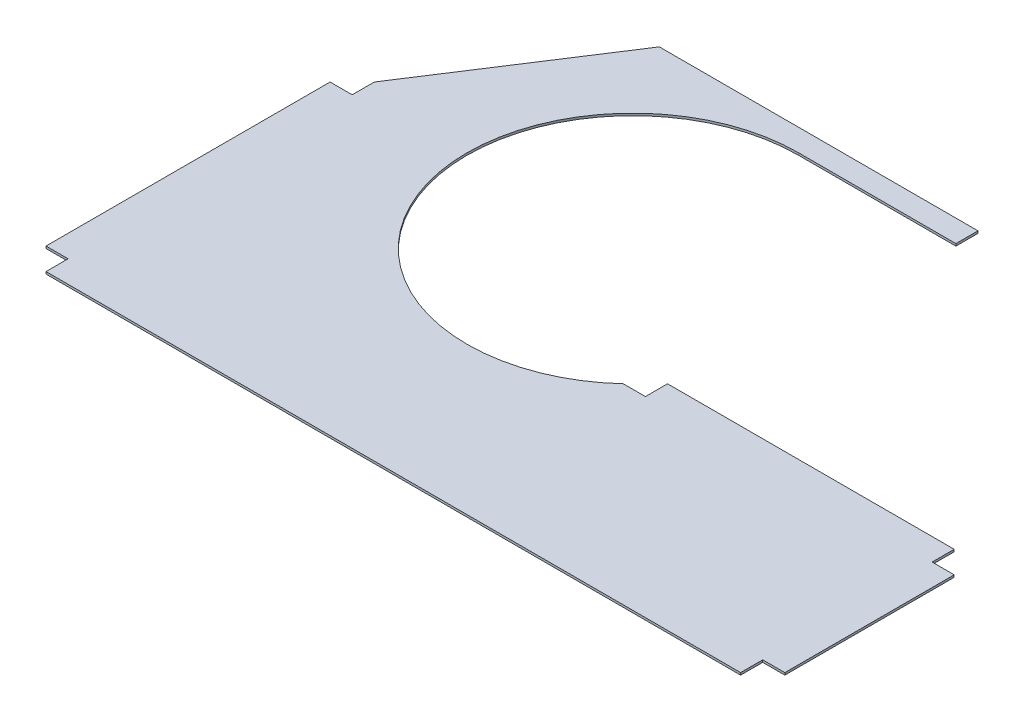
SolidWorks part; units mm, degrees
ref_plane "Front Plane" through (0, 0, 0) normal (0, 0, 1) x (1, 0, 0)
ref_plane "Top Plane" through (0, 0, 0) normal (0, 1, 0) x (1, 0, 0)
ref_plane "Right Plane" through (0, 0, 0) normal (1, 0, 0) x (0, 0, -1)
sketch "Sketch1" plane through (0, 0, 0) normal (0, 1, 0) x (1, 0, 0)
  line L0 (0, 0) -> (20, 0)
  line L1 (20, 0) -> (20, -20)
  line L2 (20, -20) -> (648.38, -20)
  line L3 (648.38, -20) -> (648.38, 0)
  line L4 (648.38, 0) -> (668.38, 0)
  line L5 (668.38, 0) -> (668.38, 153.21)
  line L7 (0, 0) -> (0, 257)
  line L9 (121.3895, 433.4594) -> (409.6583, 433.4594)
  line L10 (267.3398, 413.4594) -> (409.6583, 413.4594)
  line L11 (409.6583, 433.4594) -> (409.6583, 413.4594)
  line L12 (0, 257) -> (20, 257)
  line L13 (20, 257) -> (20, 277)
  line L14 (20, 277) -> (121.3895, 433.4594)
  line L15 (668.38, 153.21) -> (648.38, 153.21)
  line L16 (648.38, 153.21) -> (648.38, 173.21)
  line L18 (648.38, 173.21) -> (389.0505, 173.21)
  line L19 (389.0505, 173.21) -> (389.0505, 153.21)
  line L20 (389.0505, 153.21) -> (369.0505, 153.21)
  arc A0 (369.0505, 153.21) -> (267.3398, 413.4594) centre (267.3398, 263.4594) cw
  point P13 (0, 0)
  dimension "D13" = 150
  dimension "D1" = 628.38
  dimension "D2" = 20
  dimension "D3" = 20
  dimension "D4" = 20
  dimension "D5" = 257
  dimension "D6" = 20
  dimension "D7" = 20
  dimension "D8" = 453.4594
  dimension "D9" = 153.21
  dimension "D10" = 20
  dimension "D11" = 20
  dimension "D12" = 20
  dimension "D14" = 280.0445
  dimension "D15" = 20
  dimension "D16" = 20
extrude "Boss-Extrude1" add sketch "Sketch1" along normal blind 2
